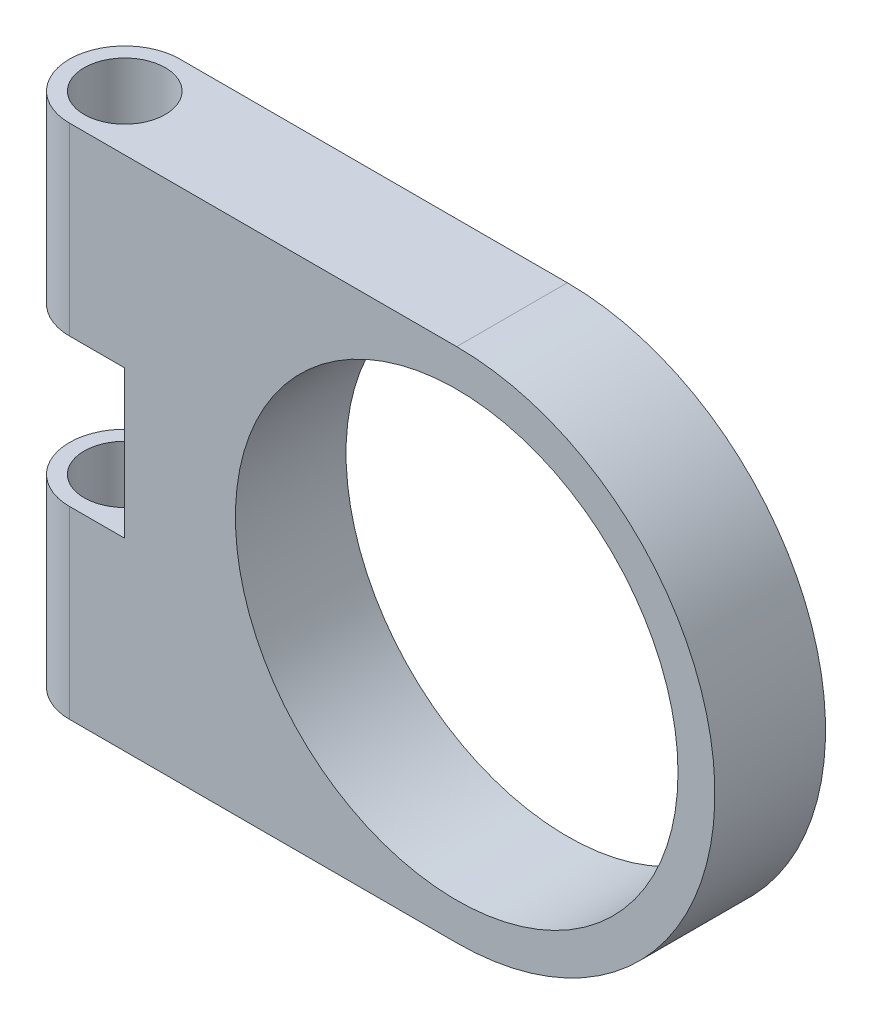
SolidWorks part; units mm, degrees
ref_plane "Front Plane" through (0, 0, 0) normal (0, 0, 1) x (1, 0, 0)
ref_plane "Top Plane" through (0, 0, 0) normal (0, 1, 0) x (1, 0, 0)
ref_plane "Right Plane" through (0, 0, 0) normal (1, 0, 0) x (0, 0, -1)
sketch "Profile Sketch" plane through (0, 0, 0) normal (0, 0, 1) x (1, 0, 0)
  line L0 (-60, 35) -> (0, 35)
  line L1 (-60, 35) -> (-60, -35)
  line L2 (-60, -35) -> (0, -35)
  line L3 (-35, 30) -> (-35, -30) construction
  line L4 (-35, 30) -> (0, 30) construction
  line L5 (-35, -30) -> (0, -30) construction
  circle A0 centre (0, 0) radius 30
  arc A1 (-18.0278, 30) -> (-18.0278, -30) centre (0, 0) ccw construction
  arc A2 (0, -35) -> (0, 35) centre (0, 0) ccw
  dimension "D1" = 60
  dimension "D2" = 5
  dimension "D3" = 25
extrude "Profile Extrude" add sketch "Profile Sketch" against normal blind 15
sketch "Hole Sketch" plane through (0, 35, 0) normal (0, 1, 0) x (1, 0, 0)
  line L0 (-60, 15) -> (-60, 0) construction
  line L1 (-60, 7.5) -> (-52.5, 7.5) construction
  circle A0 centre (-52.5, 7.5) radius 5.5
  dimension "D1" = 11
  dimension "D2" = 7.5
extrude "Hole Cut" cut sketch "Hole Sketch" against normal up to surface (70 mm away) up to face at (-30, -35, -7.5)
sketch "Gap Sketch" plane through (0, 0, 0) normal (0, 1, 0) x (1, 0, 0)
  line L0 (-60, 15) -> (-60, 0) construction
  line L4 (0, 0) -> (-60, 0) construction
  line L5 (0, 15) -> (-60, 15) construction
  line L6 (-45, 0) -> (-45, 15)
  line L7 (-45, 0) -> (-60, 0)
  line L8 (-60, 0) -> (-60, 15)
  line L9 (-60, 15) -> (-45, 15)
  circle A0 centre (-52.5, 7.5) radius 7.5 construction
extrude "Gap Cut" cut sketch "Gap Sketch" against normal blind 10 and the other way blind 10
fillet "Upper Fillet" 2 edges at (-60, 22.5, 0) (-60, 22.5, -15) type full round first side face at (-36.875, 0, 0) second side face at (30, 0, -15) middle face at (-60, 22.5, -7.5)
fillet "Lower Fillet" 2 edges at (-60, -22.5, -15) (-60, -22.5, 0) type full round first side face at (30, 0, -15) second side face at (-35, 0, 0) middle face at (-60, -22.5, -7.5)
